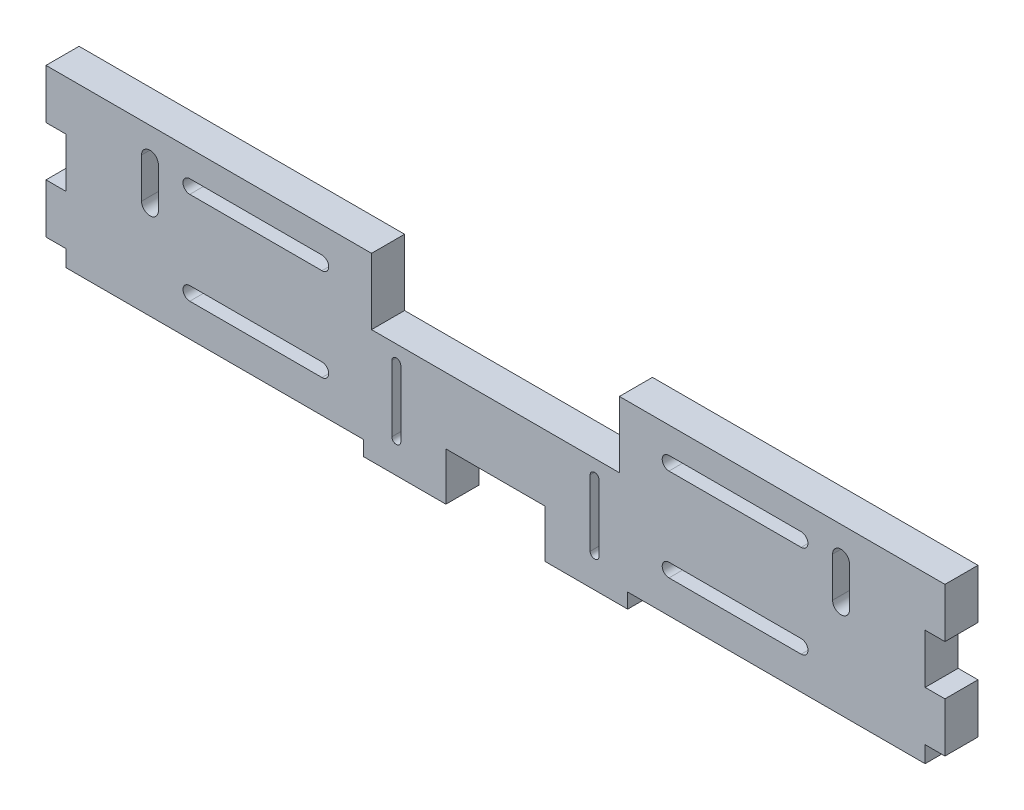
SolidWorks part; units mm, degrees
ref_plane "前基準面" through (0, 0, 0) normal (0, 0, 1) x (1, 0, 0)
ref_plane "上基準面" through (0, 0, 0) normal (0, 1, 0) x (1, 0, 0)
ref_plane "右基準面" through (0, 0, 0) normal (1, 0, 0) x (0, 0, -1)
sketch "草圖1" plane through (0, 0, 0) normal (0, 0, 1) x (1, 0, 0)
  line L0 (136, -22.5) -> (136, -7.5)
  line L1 (136, 22.5) -> (-136, 22.5)
  line L2 (130, 7.5) -> (130, -7.5)
  line L3 (130, -27.5) -> (-130, -27.5)
  line L4 (-130, 7.5) -> (-130, -7.5)
  line L5 (0, -27.5) -> (0, 22.5) construction
  line L6 (130, 0) -> (-130, 0) construction
  line L9 (-130, 7.5) -> (-136, 7.5)
  line L10 (-136, 22.5) -> (-136, 7.5)
  line L14 (-136, -22.5) -> (-136, -7.5)
  line L15 (130, -7.5) -> (136, -7.5)
  line L16 (130, 7.5) -> (136, 7.5)
  line L17 (136, 22.5) -> (136, 7.5)
  line L18 (-136, -22.5) -> (-130, -22.5)
  line L19 (-130, -22.5) -> (-130, -27.5)
  line L20 (-136, -7.5) -> (-130, -7.5)
  line L21 (130, -22.5) -> (130, -27.5)
  line L22 (130, -22.5) -> (136, -22.5)
  line L23 (-30, -22.5) -> (-30, -2.5) construction
  line L24 (-31.35, -22.5) -> (-31.35, -2.5)
  line L25 (-28.65, -22.5) -> (-28.65, -2.5)
  line L26 (30, -22.5) -> (30, -2.5) construction
  line L27 (31.35, -22.5) -> (31.35, -2.5)
  line L28 (28.65, -22.5) -> (28.65, -2.5)
  arc A0 (-31.35, -22.5) -> (-28.65, -22.5) centre (-30, -22.5) ccw
  arc A1 (-28.65, -2.5) -> (-31.35, -2.5) centre (-30, -2.5) ccw
  arc A2 (31.35, -22.5) -> (28.65, -22.5) centre (30, -22.5) cw
  arc A3 (28.65, -2.5) -> (31.35, -2.5) centre (30, -2.5) cw
  point P0 (0, 0)
  point P8 (0, 0)
  point P13 (-136, -15)
  point P14 (136, -15)
  point P24 (-30, -12.5)
  point P31 (30, -12.5)
  dimension "D8" = 1.35
  dimension "D1" = 260
  dimension "D2" = 6
  dimension "D3" = 15
  dimension "D4" = 6
  dimension "D5" = 50
  dimension "D6" = 5
  dimension "D7" = 20
  dimension "D9" = 5
  dimension "D10" = 30
extrude "填料-伸長1" add sketch "草圖1" along normal blind 10
sketch "草圖2" plane through (0, 0, 10) normal (0, 0, 1) x (1, 0, 0)
  line L0 (-92.5, 12.5) -> (-52.5, 12.5) construction
  line L1 (-92.5, 14.55) -> (-52.5, 14.55)
  line L2 (-92.5, 10.45) -> (-52.5, 10.45)
  line L3 (-130, 7.5) -> (-130, -7.5) construction
  line L6 (0, 61.8937) -> (0, -44.053) construction
  line L7 (-92.5, -15.5) -> (-52.5, -15.5) construction
  line L8 (-92.5, -13.45) -> (-52.5, -13.45)
  line L11 (-92.5, -17.55) -> (-52.5, -17.55)
  line L14 (-87.5, 12.5) -> (-81.5, 12.5) construction
  line L15 (-46.5, 24.5) -> (-98.5, 24.5) construction
  line L16 (-46.5, 24.5) -> (-46.5, -27.5) construction
  line L17 (-46.5, -27.5) -> (-98.5, -27.5) construction
  line L18 (-98.5, 24.5) -> (-98.5, -27.5) construction
  line L19 (-72.5, -27.5) -> (-72.5, 24.5) construction
  line L20 (-46.5, -1.5) -> (-98.5, -1.5) construction
  line L21 (-87.5, 14.5) -> (-81.5, 14.5) construction
  line L22 (-87.5, 10.5) -> (-81.5, 10.5) construction
  line L23 (-57.5, 12.5) -> (-63.5, 12.5) construction
  line L24 (-57.5, 14.5) -> (-63.5, 14.5) construction
  line L25 (-57.5, 10.5) -> (-63.5, 10.5) construction
  line L26 (-57.5, -15.5) -> (-63.5, -15.5) construction
  line L27 (-57.5, -17.5) -> (-63.5, -17.5) construction
  line L28 (-57.5, -13.5) -> (-63.5, -13.5) construction
  line L29 (-87.5, -15.5) -> (-81.5, -15.5) construction
  line L30 (-87.5, -17.5) -> (-81.5, -17.5) construction
  line L31 (-87.5, -13.5) -> (-81.5, -13.5) construction
  line L32 (-130, -27.5) -> (130, -27.5) construction
  line L33 (92.5, 12.5) -> (52.5, 12.5) construction
  line L34 (92.5, 14.55) -> (52.5, 14.55)
  line L35 (92.5, 10.45) -> (52.5, 10.45)
  line L36 (92.5, -15.5) -> (52.5, -15.5) construction
  line L37 (92.5, -13.45) -> (52.5, -13.45)
  line L38 (92.5, -17.55) -> (52.5, -17.55)
  arc A0 (-92.5, 14.55) -> (-92.5, 10.45) centre (-92.5, 12.5) ccw
  arc A1 (-52.5, 10.45) -> (-52.5, 14.55) centre (-52.5, 12.5) ccw
  arc A8 (-87.5, 14.5) -> (-87.5, 10.5) centre (-87.5, 12.5) ccw construction
  arc A9 (-81.5, 10.5) -> (-81.5, 14.5) centre (-81.5, 12.5) ccw construction
  arc A10 (-57.5, 14.5) -> (-57.5, 10.5) centre (-57.5, 12.5) cw construction
  arc A11 (-63.5, 10.5) -> (-63.5, 14.5) centre (-63.5, 12.5) cw construction
  arc A12 (-57.5, -17.5) -> (-57.5, -13.5) centre (-57.5, -15.5) ccw construction
  arc A13 (-63.5, -13.5) -> (-63.5, -17.5) centre (-63.5, -15.5) ccw construction
  arc A14 (-87.5, -17.5) -> (-87.5, -13.5) centre (-87.5, -15.5) cw construction
  arc A15 (-81.5, -13.5) -> (-81.5, -17.5) centre (-81.5, -15.5) cw construction
  arc A16 (-92.5, -13.45) -> (-92.5, -17.55) centre (-92.5, -15.5) ccw
  arc A17 (-52.5, -17.55) -> (-52.5, -13.45) centre (-52.5, -15.5) ccw
  arc A18 (92.5, 14.55) -> (92.5, 10.45) centre (92.5, 12.5) cw
  arc A19 (52.5, 10.45) -> (52.5, 14.55) centre (52.5, 12.5) cw
  arc A20 (92.5, -13.45) -> (92.5, -17.55) centre (92.5, -15.5) cw
  arc A21 (52.5, -17.55) -> (52.5, -13.45) centre (52.5, -15.5) cw
  point P2 (-72.5, 12.5)
  point P7 (-66.3741, -47.1865)
  point P8 (0, 0)
  point P9 (0, 0)
  point P10 (-62.4886, 12.5)
  point P11 (-72.7843, -42.5258)
  point P12 (0, 0)
  point P13 (-67.2455, -46.2896)
  point P16 (-44.3382, -53.7505)
  point P17 (-58.1949, 12.5)
  point P19 (-164.7034, 12.5)
  point P21 (-72.5, -1.5)
  point P23 (0, 0)
  point P24 (0, 0)
  point P25 (0, 0)
  point P26 (0, 0)
  point P27 (0, 0)
  point P28 (0, 0)
  point P29 (0, 0)
  point P30 (-72.5, 12.5)
  point P33 (-72.5, -15.5)
  point P41 (-84.5, 12.5)
  point P49 (-79.5, 12.5)
  point P50 (-65.5, 12.5)
  point P51 (-89.5, 12.5)
  point P54 (-60.5, 12.5)
  point P61 (-60.5, -15.5)
  point P68 (-84.5, -15.5)
  point P75 (-47.6913, 102.6486)
  point P76 (-116.4246, 115.6244)
  point P77 (-72.5, -0.6916)
  point P80 (-73.2455, -1.5)
  point P81 (0, 0)
  point P84 (0, 0)
  point P85 (-72.5, -15.5)
  point P86 (0, 0)
  point P89 (72.5, 12.5)
  point P96 (72.5, -15.5)
  dimension "D3" = 31.5
  dimension "D2" = 4.1
  dimension "D4" = 40
  dimension "D7" = 52
  dimension "D8" = 52
  dimension "D9" = 14
  dimension "D10" = 10
  dimension "D11" = 4
  dimension "D12" = 10
  dimension "D13" = 24
extrude "除料-伸長1" cut sketch "草圖2" against normal through all
sketch "草圖3" plane through (0, 0, 10) normal (0, 0, 1) x (1, 0, 0)
  line L0 (0, 40.44) -> (0, -35.44) construction
  line L1 (-130, -27.5) -> (130, -27.5) construction
  line L2 (15, -17.5) -> (-15, -17.5)
  line L3 (15, -17.5) -> (15, -27.5)
  line L4 (15, -27.5) -> (-15, -27.5)
  line L5 (-15, -17.5) -> (-15, -27.5)
  line L6 (0, -27.5) -> (0, -17.5) construction
  line L7 (15, -22.5) -> (-15, -22.5) construction
  line L8 (136, 22.5) -> (-136, 22.5) construction
  line L9 (-37.5, 22.5) -> (37.5, 22.5)
  line L10 (-37.5, 22.5) -> (-37.5, 2.5)
  line L11 (-37.5, 2.5) -> (37.5, 2.5)
  line L12 (37.5, 22.5) -> (37.5, 2.5)
  circle A0 centre (0, 40.44) radius 36 construction
  point P3 (0, -22.5)
  point P16 (0, 2.5)
  dimension "D3" = 72
  dimension "D1" = 10
  dimension "D2" = 30
  dimension "D4" = 67.94
  dimension "D5" = 20
  dimension "D6" = 75
extrude "除料-伸長2" cut sketch "草圖3" against normal through all
sketch "草圖4" plane through (0, -27.5, 0) normal (0, -1, 0) x (1, 0, 0)
  line L0 (-130, 0) -> (-15, 0) construction
  line L1 (-15, 10) -> (-40, 10)
  line L2 (-15, 10) -> (-15, 0)
  line L3 (-15, 0) -> (-40, 0)
  line L4 (-40, 10) -> (-40, 0)
  line L5 (0, 39.3448) -> (0, -9.8344) construction
  line L6 (15, 0) -> (40, 0)
  line L7 (40, 10) -> (40, 0)
  line L8 (15, 10) -> (40, 10)
  line L9 (15, 10) -> (15, 0)
  dimension "D1" = 25
  dimension "D2" = 30
extrude "填料-伸長2" add sketch "草圖4" along normal blind 4.5
sketch "草圖5" plane through (0, 0, 10) normal (0, 0, 1) x (1, 0, 0)
  line L0 (-46.5, -27.5) -> (-98.5, -27.5) construction
  line L1 (-46.5, -27.5) -> (-46.5, 24.5) construction
  line L2 (-46.5, 24.5) -> (-98.5, 24.5) construction
  line L3 (-98.5, -27.5) -> (-98.5, 24.5) construction
  line L4 (-112.3, 7.4) -> (-99.5, 7.4) construction
  line L5 (-112.3, 20) -> (-99.5, 20) construction
  line L6 (-112.3, 20) -> (-112.3, -5.2) construction
  line L7 (-112.3, -5.2) -> (-99.5, -5.2) construction
  line L8 (-99.5, 20) -> (-99.5, -5.2) construction
  line L9 (-107.1, 13.45) -> (-107.1, 1.35)
  line L10 (-102, 1.35) -> (-102, 13.45)
  line L11 (0, 35.1152) -> (0, -35.1152) construction
  line L12 (107.1, 13.45) -> (107.1, 1.35)
  line L13 (102, 1.35) -> (102, 13.45)
  line L14 (-130, -27.5) -> (-40, -27.5) construction
  line L15 (-136, 22.5) -> (-136, 7.5) construction
  arc A0 (-102, 13.45) -> (-107.1, 13.45) centre (-104.55, 13.45) ccw
  arc A1 (-107.1, 1.35) -> (-102, 1.35) centre (-104.55, 1.35) ccw
  arc A2 (102, 13.45) -> (107.1, 13.45) centre (104.55, 13.45) cw
  arc A3 (107.1, 1.35) -> (102, 1.35) centre (104.55, 1.35) cw
  point P12 (-104.55, 3.9)
  point P13 (-104.55, 10.9)
  point P16 (-104.55, 16)
  point P18 (-107.1, 13.45)
  point P21 (-102, 13.45)
  dimension "D5" = 5.1
  dimension "D1" = 52
  dimension "D2" = 52
  dimension "D3" = 12.8
  dimension "D4" = 7
  dimension "D6" = 4
  dimension "D7" = 2.5
  dimension "D8" = 1
  dimension "D9" = 12.1
  dimension "D10" = 47.5
  dimension "D11" = 37.5
extrude "除料-伸長3" cut sketch "草圖5" against normal through all
